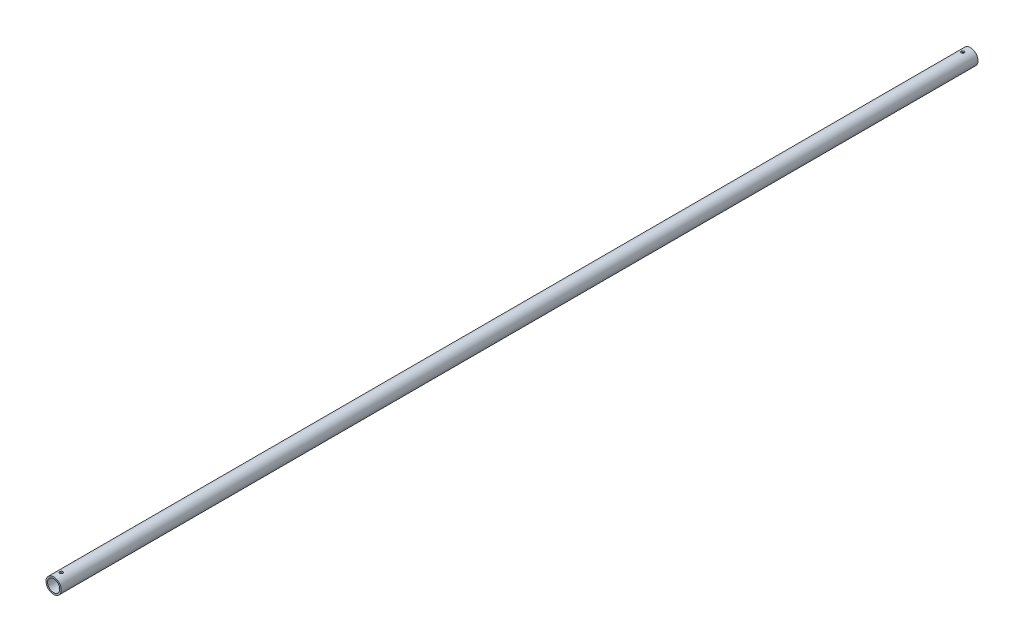
SolidWorks part; units mm, degrees
material "Thornel Mat VMA"
ref_plane "前视基准面" through (0, 0, 0) normal (0, 0, 1) x (1, 0, 0)
ref_plane "上视基准面" through (0, 0, 0) normal (0, 1, 0) x (1, 0, 0)
ref_plane "右视基准面" through (0, 0, 0) normal (1, 0, 0) x (0, 0, -1)
sketch "草图1" plane through (0, 0, 0) normal (0, 0, 1) x (1, 0, 0)
  circle A0 centre (0, 0) radius 4
  circle A1 centre (0, 0) radius 5
  dimension "D1" = 8
  dimension "D2" = 10
extrude "凸台-拉伸1" add sketch "草图1" along normal blind 300 and the other way blind 300
sketch "草图3" plane through (0, 0, 0) normal (0, 1, 0) x (1, 0, 0)
  line L0 (5, 300) -> (-5, 300) construction
  line L1 (-1000, 0) -> (49000, 0) construction
  circle A0 centre (0, 295) radius 1
  circle A1 centre (0, -295) radius 1
  dimension "D1" = 2
  dimension "D2" = 5
extrude "切除-拉伸2" cut sketch "草图3" against normal through all and the other way through all
sketch "草图6" plane through (0, 0, 0) normal (0, 1, 0) x (1, 0, 0)
  circle A0 centre (0, 0) radius 17.2534
